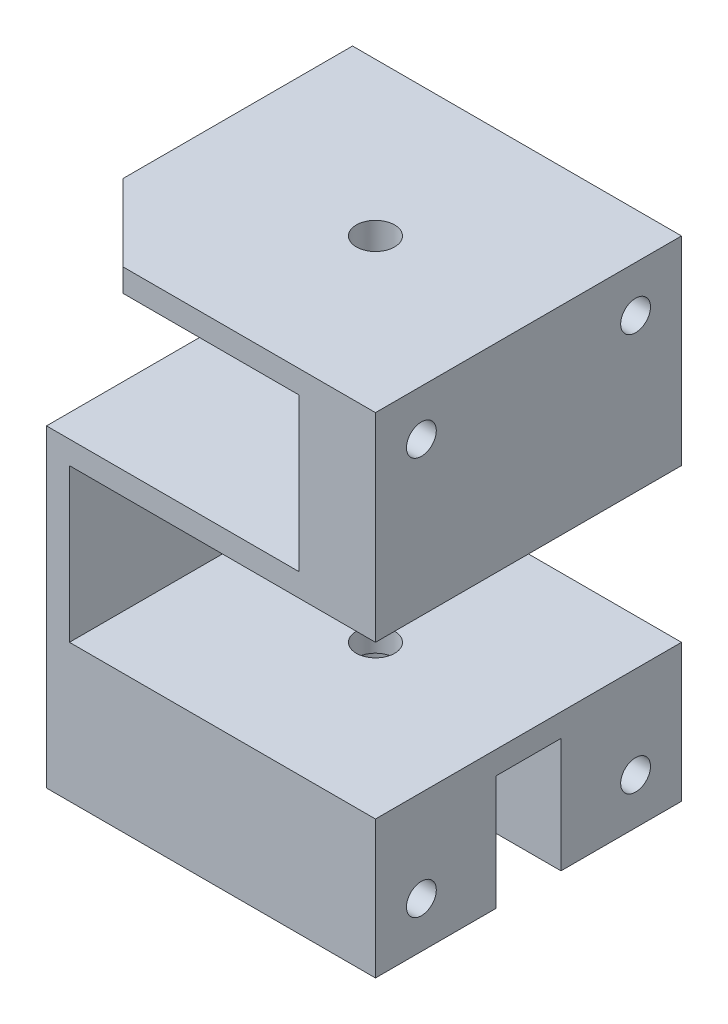
SolidWorks part; units mm, degrees
ref_plane "Front Plane" through (0, 0, 0) normal (0, 0, 1) x (1, 0, 0)
ref_plane "Top Plane" through (0, 0, 0) normal (0, 1, 0) x (1, 0, 0)
ref_plane "Right Plane" through (0, 0, 0) normal (1, 0, 0) x (0, 0, -1)
sketch "Sketch1" plane through (0, 0, 0) normal (0, 0, 1) x (1, 0, 0)
  line L0 (0, 0) -> (-40, 0)
  line L1 (-40, 0) -> (-40, 20)
  line L2 (-40, 20) -> (0, 20)
  line L3 (0, 20) -> (0, 46)
  line L4 (0, 46) -> (-43, 46)
  line L5 (0, 0) -> (0, -18)
  line L6 (0, -18) -> (-43, -18)
  line L7 (-43, 23) -> (-43, -18)
  line L8 (-43, 23) -> (-10, 23)
  line L9 (-10, 23) -> (-10, 43)
  line L10 (-10, 43) -> (-43, 43)
  line L11 (-43, 43) -> (-43, 46)
  dimension "D1" = 20
  dimension "D2" = 40
  dimension "D3" = 40
  dimension "D4" = 3
  dimension "D5" = 3
  dimension "D6" = 20
  dimension "D7" = 3
  dimension "D8" = 18
  dimension "D9" = 10
extrude "Boss-Extrude1" add sketch "Sketch1" along normal blind 40
sketch "Sketch3" plane through (0, 20, 0) normal (0, -1, 0) x (-1, 0, 0)
  line L0 (40, -40) -> (0, 0) construction
  circle A0 centre (20, -20) radius 2.5
  dimension "D1" = 5
extrude "Cut-Extrude1" cut sketch "Sketch3" against normal through all both and the other way through all
sketch "Sketch4" plane through (0, -18, 0) normal (0, -1, 0) x (-1, 0, 0)
  line L0 (20, -24.25) -> (0, -24.25)
  line L1 (0, -40) -> (0, 0) construction
  line L2 (0, -24.25) -> (0, -15.75)
  line L3 (0, -15.75) -> (20, -15.75)
  arc A0 (20, -24.25) -> (20, -15.75) centre (20, -20) ccw
  dimension "D1" = 8.5
extrude "Cut-Extrude2" cut sketch "Sketch4" against normal blind 15
sketch "Sketch5" plane through (0, 23, 0) normal (0, 1, 0) x (1, 0, 0)
  circle A0 centre (-20, -20) radius 2.5
  circle A1 centre (-20, -20) radius 3.5
  dimension "D1" = 7
extrude "Boss-Extrude2" add sketch "Sketch5" along normal blind 0.5
sketch "Sketch6" plane through (0, 43, 0) normal (0, -1, 0) x (-1, 0, 0)
  circle A0 centre (20, -20) radius 2.5
  circle A1 centre (20, -20) radius 3.5
  dimension "D1" = 7
extrude "Boss-Extrude3" add sketch "Sketch6" along normal blind 0.5
chamfer "Chamfer1" distance 0.5 angle 45 2 edges at (-20, 23, 16.5) (-20, 43, 23.5)
sketch "Sketch7" plane through (-40, 0, 0) normal (1, 0, 0) x (0, 0, -1)
  line L0 (-40, 20) -> (0, 0) construction
  line L1 (-22.5, 10) -> (-17.5, 10) construction
  line L2 (-22.5, 12.25) -> (-17.5, 12.25)
  line L3 (-22.5, 7.75) -> (-17.5, 7.75)
  arc A0 (-22.5, 12.25) -> (-22.5, 7.75) centre (-22.5, 10) ccw
  arc A1 (-17.5, 7.75) -> (-17.5, 12.25) centre (-17.5, 10) ccw
  point P6 (-20, 10)
  dimension "D1" = 2.25
  dimension "D2" = 5
extrude "Cut-Extrude3" cut sketch "Sketch7" against normal blind 4.1593
sketch "Sketch9" plane through (0, 0, 0) normal (0, 0, -1) x (-1, 0, 0)
  line L1 (0, 46) -> (43, 46)
  line L2 (0, 46) -> (0, 23)
  line L3 (0, 23) -> (43, 23)
  line L4 (43, 46) -> (43, 23)
extrude "Boss-Extrude4" add sketch "Sketch9" against normal blind 9
chamfer "Chamfer2" distance 3 angle 45 1 edges at (-10, 33, 9)
sketch "Sketch8" plane through (0, 0, 0) normal (1, 0, 0) x (0, 0, -1)
  line L0 (-34, 40) -> (-34, -12) construction
  line L1 (-34, -12) -> (-6, -12) construction
  line L2 (-6, -12) -> (-6, 40) construction
  line L3 (-6, 40) -> (-34, 40) construction
  line L4 (-40, 46) -> (0, 46) construction
  line L5 (0, 20) -> (0, 46) construction
  line L6 (-40, 20) -> (-40, 46) construction
  line L7 (-15.75, -18) -> (0, -18) construction
  circle A0 centre (-34, 40) radius 1.95
  circle A1 centre (-6, 40) radius 1.95
  circle A2 centre (-34, -12) radius 1.95
  circle A3 centre (-6, -12) radius 1.95
  dimension "D1" = 3.9
  dimension "D2" = 6
  dimension "D3" = 6
  dimension "D4" = 6
  dimension "D5" = 6
extrude "Cut-Extrude4" cut sketch "Sketch8" against normal blind 9
chamfer "Chamfer5" distance 10 angle 45 1 edges at (-43, 44.5, 40)
